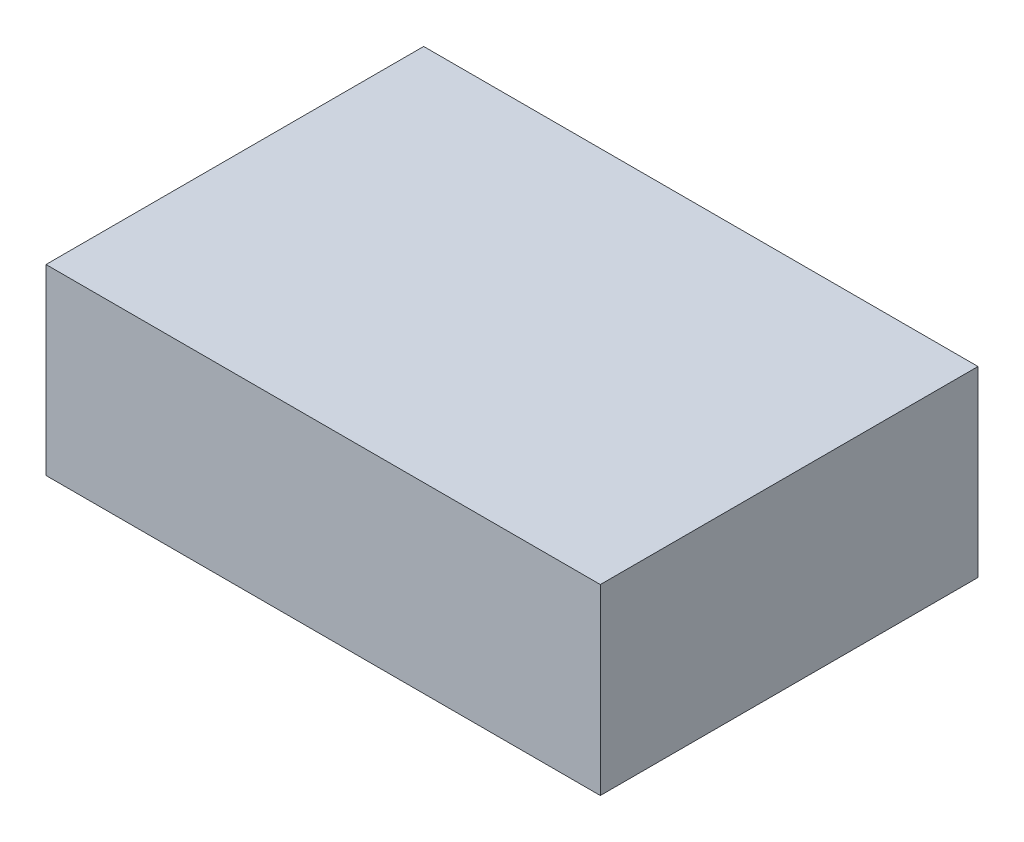
SolidWorks part; units mm, degrees
ref_plane "Front Plane" through (0, 0, 0) normal (0, 0, 1) x (1, 0, 0)
ref_plane "Top Plane" through (0, 0, 0) normal (0, 1, 0) x (1, 0, 0)
ref_plane "Right Plane" through (0, 0, 0) normal (1, 0, 0) x (0, 0, -1)
sketch "Sketch1" plane through (0, 0, 0) normal (0, 1, 0) x (1, 0, 0)
  line L1 (0, 0) -> (91, 0)
  line L2 (0, 0) -> (0, 62)
  line L3 (0, 62) -> (91, 62)
  line L4 (91, 0) -> (91, 62)
  dimension "D1" = 91
  dimension "D2" = 62
extrude "Boss-Extrude1" add sketch "Sketch1" along normal blind 30
